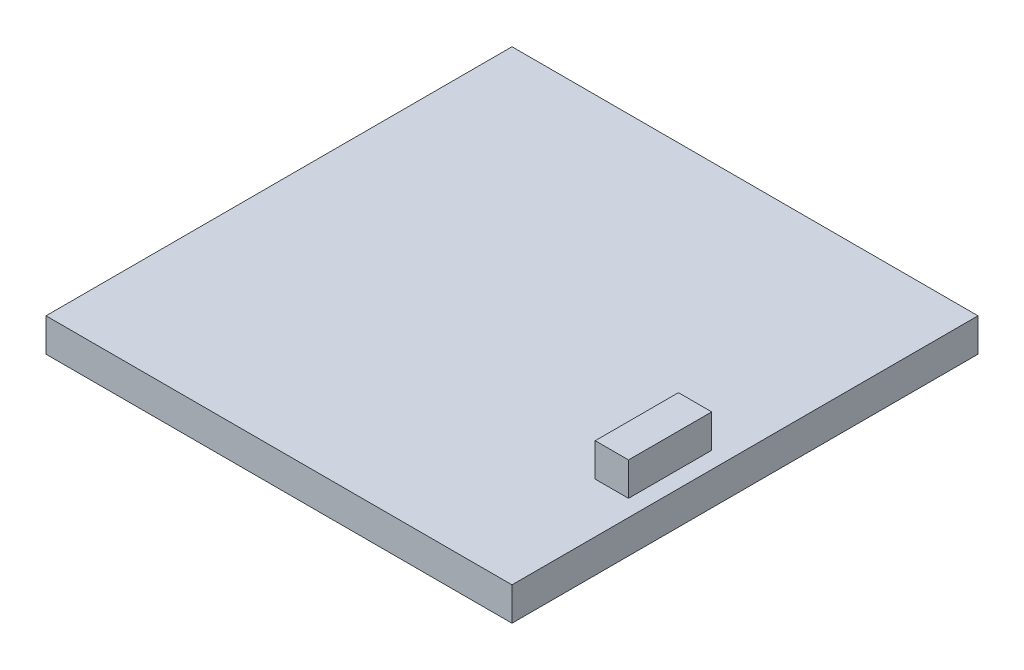
SolidWorks part; units mm, degrees
ref_plane "Front Plane" through (0, 0, 0) normal (0, 0, 1) x (1, 0, 0)
ref_plane "Top Plane" through (0, 0, 0) normal (0, 1, 0) x (1, 0, 0)
ref_plane "Right Plane" through (0, 0, 0) normal (1, 0, 0) x (0, 0, -1)
sketch "Sketch1" plane through (0, 0, 0) normal (0, 1, 0) x (1, 0, 0)
  line L1 (-355.6, -355.6) -> (355.6, -355.6)
  line L2 (-355.6, -355.6) -> (-355.6, 355.6)
  line L3 (-355.6, 355.6) -> (355.6, 355.6)
  line L4 (355.6, -355.6) -> (355.6, 355.6)
  line L5 (-355.6, -355.6) -> (355.6, 355.6) construction
  line L6 (-355.6, 355.6) -> (355.6, -355.6) construction
  point P0 (0, 0)
  dimension "D1" = 711.2
  dimension "D2" = 711.2
extrude "Boss-Extrude1" add sketch "Sketch1" along normal blind 50.8
sketch "Sketch2" plane through (0, 50.8, 0) normal (0, 1, 0) x (1, 0, 0)
  line L0 (355.6, -355.6) -> (355.6, 355.6) construction
  line L1 (330.2, -152.4) -> (279.4, -152.4)
  line L2 (330.2, -152.4) -> (330.2, -25.4)
  line L3 (330.2, -25.4) -> (279.4, -25.4)
  line L4 (279.4, -152.4) -> (279.4, -25.4)
  line L6 (-355.6, -355.6) -> (355.6, -355.6) construction
  dimension "D1" = 50.8
  dimension "D2" = 127
  dimension "D3" = 25.4
  dimension "D4" = 203.2
extrude "Boss-Extrude2" add sketch "Sketch2" along normal blind 50.8
